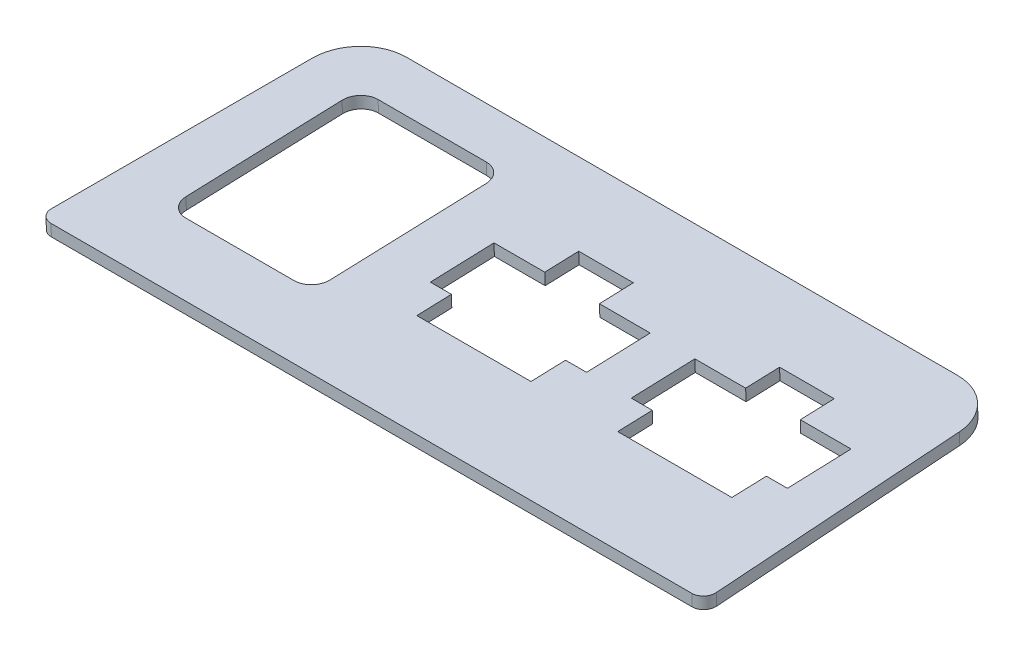
SolidWorks part; units mm, degrees
ref_plane "Front Plane" through (0, 0, 0) normal (0, 0, 1) x (1, 0, 0)
ref_plane "Top Plane" through (0, 0, 0) normal (0, 1, 0) x (1, 0, 0)
ref_plane "Right Plane" through (0, 0, 0) normal (1, 0, 0) x (0, 0, -1)
sketch "Sketch1" plane through (0, -69.7404, -2.4354) normal (0, 0.9994, 0.0349) x (1, 0, 0)
  line L1 (56.175, -2.8069) -> (-56.175, -2.8069) construction
  line L4 (-46.8331, 44.5513) -> (46.8331, 44.5513) construction
  line L6 (50.8306, 40.6909) -> (52.0304, 6.3327) construction
  line L7 (-52.0304, 6.3327) -> (-50.8306, 40.6909) construction
  line L8 (-55.4003, -4.2069) -> (55.4003, -4.2069)
  line L9 (55.4003, -4.2069) -> (53.8625, 39.8305)
  line L10 (45.8674, 47.5513) -> (-45.8674, 47.5513)
  line L11 (-53.8625, 39.8305) -> (-55.4003, -4.2069)
  arc A4 (53.8625, 39.8305) -> (45.8674, 47.5513) centre (45.8674, 39.5513) ccw
  arc A5 (-45.8674, 47.5513) -> (-53.8625, 39.8305) centre (-45.8674, 39.5513) ccw
  dimension "D4" = 8
  dimension "D1" = 3
  dimension "D2" = 3
  dimension "D3" = 3
  dimension "D5" = 1.4
extrude "Boss-Extrude1" add sketch "Sketch1" along normal blind 2
sketch "Sketch2" plane through (0, -69.7404, -2.4354) normal (0, -0.9994, -0.0349) x (1, 0, 0)
  line L0 (-4.05, -28.7222) -> (-4.05, -34.3722)
  line L1 (-42.4354, -7.3722) -> (-24.4354, -7.3722)
  line L2 (-45.4354, -10.3722) -> (-45.4354, -36.3722)
  line L3 (-42.4354, -39.3722) -> (-24.4354, -39.3722)
  line L4 (-21.4354, -10.3722) -> (-21.4354, -36.3722)
  line L5 (-12.5, -18.1222) -> (-9, -18.1222)
  line L6 (-12.5, -18.1222) -> (-12.5, -28.7222)
  line L7 (-12.5, -28.7222) -> (-4.05, -28.7222)
  line L8 (13.5, -18.1222) -> (13.5, -28.7222)
  line L9 (-9, -12.3722) -> (10, -12.3722)
  line L10 (-9, -12.3722) -> (-9, -18.1222)
  line L11 (-4.05, -34.3722) -> (5.05, -34.3722)
  line L12 (10, -12.3722) -> (10, -18.1222)
  line L13 (10, -18.1222) -> (13.5, -18.1222)
  line L14 (5.05, -28.7222) -> (5.05, -34.3722)
  line L15 (5.05, -28.7222) -> (13.5, -28.7222)
  line L16 (-13, -9.8722) -> (14, -36.8722) construction
  line L17 (-13, -9.8722) -> (14, -9.8722) construction
  line L18 (-13, -9.8722) -> (-13, -36.8722) construction
  line L19 (-13, -36.8722) -> (14, -36.8722) construction
  line L20 (14, -9.8722) -> (14, -36.8722) construction
  line L21 (17.2177, 3.7502) -> (17.2177, -36.664) construction
  line L22 (46.9354, -23.4222) -> (20.9354, -23.4222) construction
  line L23 (33.9354, -12.3722) -> (33.9354, -34.3722) construction
  line L24 (20.4354, -9.8722) -> (20.4354, -36.8722) construction
  line L25 (47.4354, -36.8722) -> (20.4354, -36.8722) construction
  line L26 (47.4354, -9.8722) -> (47.4354, -36.8722) construction
  line L27 (47.4354, -9.8722) -> (20.4354, -9.8722) construction
  line L28 (-47.4354, -23.3722) -> (-45.4354, -23.3722) construction
  line L29 (-47.4354, -5.3722) -> (-19.4354, -5.3722) construction
  line L30 (-47.4354, -5.3722) -> (-47.4354, -41.3722) construction
  line L31 (-47.4354, -41.3722) -> (-19.4354, -41.3722) construction
  line L32 (-19.4354, -5.3722) -> (-19.4354, -41.3722) construction
  line L33 (-33.4354, -7.3722) -> (-33.4354, -5.3722) construction
  line L34 (0.5, -12.3722) -> (0.5, -34.3722) construction
  line L35 (-12.5, -23.4222) -> (13.5, -23.4222) construction
  line L36 (47.4354, -9.8722) -> (20.4354, -36.8722) construction
  line L37 (29.3854, -28.7222) -> (20.9354, -28.7222)
  line L38 (29.3854, -28.7222) -> (29.3854, -34.3722)
  line L39 (24.4354, -18.1222) -> (20.9354, -18.1222)
  line L40 (24.4354, -12.3722) -> (24.4354, -18.1222)
  line L41 (38.4854, -34.3722) -> (29.3854, -34.3722)
  line L42 (43.4354, -12.3722) -> (43.4354, -18.1222)
  line L43 (43.4354, -12.3722) -> (24.4354, -12.3722)
  line L44 (20.9354, -18.1222) -> (20.9354, -28.7222)
  line L45 (46.9354, -28.7222) -> (38.4854, -28.7222)
  line L46 (46.9354, -18.1222) -> (46.9354, -28.7222)
  line L47 (46.9354, -18.1222) -> (43.4354, -18.1222)
  line L48 (38.4854, -28.7222) -> (38.4854, -34.3722)
  line L49 (20.4354, -23.3722) -> (14, -23.3722) construction
  line L51 (47.4354, -23.3722) -> (51.4354, -23.3722) construction
  line L52 (55.4003, 4.2069) -> (53.8625, -39.8305) construction
  line L53 (-46.8331, -44.5513) -> (46.8331, -44.5513) construction
  line L54 (-13, -23.3722) -> (-19.4354, -23.3722) construction
  line L55 (-33.4354, -5.3722) -> (-33.4354, -2.1931) construction
  line L56 (-33.4354, -41.3722) -> (-33.4354, -44.5513) construction
  line L57 (-53.8625, -39.8305) -> (-55.4003, 4.2069) construction
  line L58 (-47.4354, -23.3722) -> (-51.4354, -23.3722) construction
  line L59 (48.0329, -2.1931) -> (-48.0329, -2.1931) construction
  arc A0 (-45.4354, -36.3722) -> (-42.4354, -39.3722) centre (-42.4354, -36.3722) ccw
  arc A1 (-24.4354, -39.3722) -> (-21.4354, -36.3722) centre (-24.4354, -36.3722) ccw
  arc A2 (-24.4354, -7.3722) -> (-21.4354, -10.3722) centre (-24.4354, -10.3722) cw
  arc A3 (-42.4354, -7.3722) -> (-45.4354, -10.3722) centre (-42.4354, -10.3722) ccw
  point P28 (0.5, -23.3722)
  point P63 (33.9354, -23.3722)
  dimension "D1" = 3
  dimension "D2" = 32
  dimension "D3" = 24
  dimension "D4" = 28
  dimension "D5" = 36
  dimension "D6" = 26
  dimension "D7" = 22
  dimension "D8" = 10.6
  dimension "D9" = 19
  dimension "D10" = 9.1
  dimension "D11" = 5.75
  dimension "D12" = 27
  dimension "D13" = 27
  dimension "D14" = 4
  dimension "D15" = 3
  dimension "D16" = 3
extrude "Cut-Extrude1" cut sketch "Sketch2" against normal up to next
fillet "Fillet1" radius 2 2 edges at (-55.4003, -68.8878, 1.8038) (55.4003, -68.8878, 1.8038)
